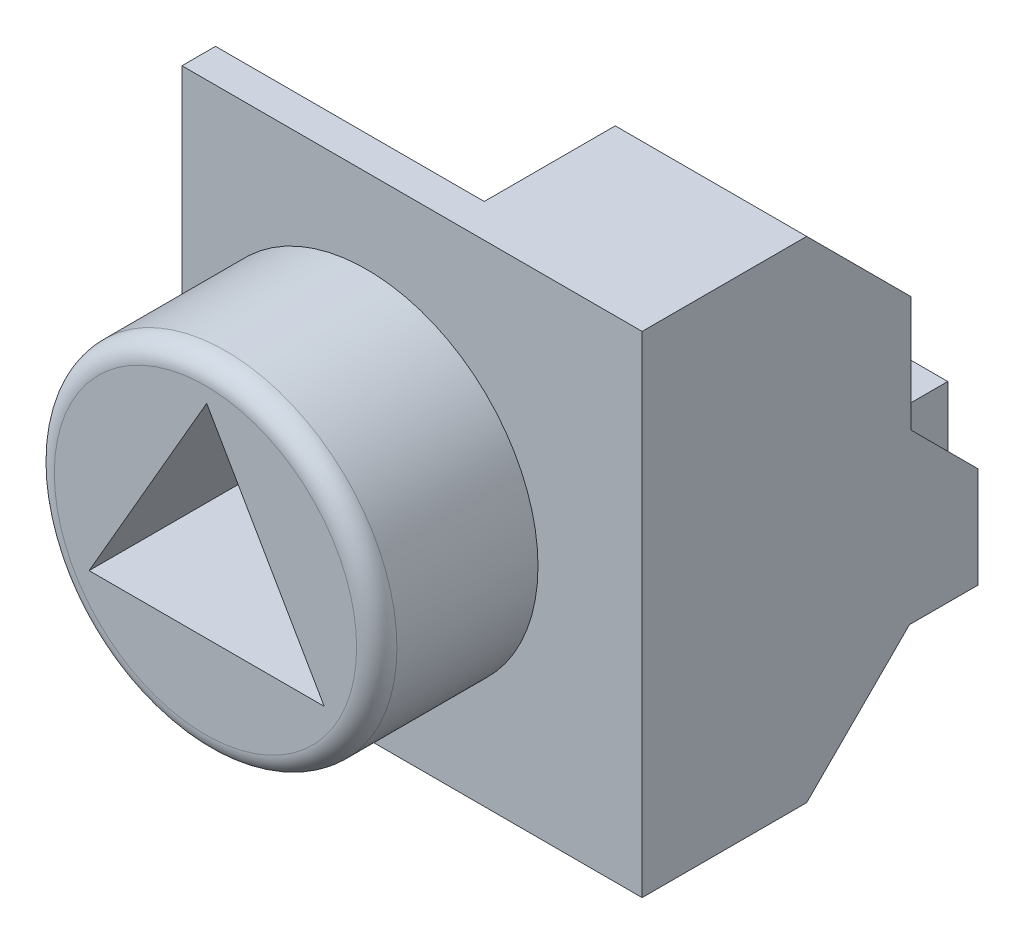
SolidWorks part; units mm, degrees
ref_plane "Спереди" through (0, 0, 0) normal (0, 0, 1) x (1, 0, 0)
ref_plane "Сверху" through (0, 0, 0) normal (0, 1, 0) x (1, 0, 0)
ref_plane "Справа" through (0, 0, 0) normal (1, 0, 0) x (0, 0, -1)
sketch "Эскиз1" plane through (0, 0, 0) normal (0, 0, 1) x (1, 0, 0)
  line L0 (-5, -15.52) -> (5, -15.52)
  line L1 (-5, 2.08) -> (5, 2.08)
  line L2 (0.9, -34.5) -> (0.9, 34.5)
  line L3 (5, 1.08) -> (-5, 1.08)
  line L4 (5, 17.48) -> (-5, 17.48)
  circle A0 centre (0, -6.52) radius 5.5
  circle A1 centre (0, 9.48) radius 5.5
  arc A2 (3.6151, 7.0385) -> (5.2151, 7.0385) centre (4.4151, 7.0385) ccw
  arc A3 (5.2151, 7.0385) -> (3.6151, 7.0385) centre (4.4151, 7.0385) ccw
  arc A4 (3.6151, -8.9615) -> (5.2151, -8.9615) centre (4.4151, -8.9615) ccw
  arc A5 (5.2151, -8.9615) -> (3.6151, -8.9615) centre (4.4151, -8.9615) ccw
sketch "Эскиз2" plane through (0, 0, 0) normal (0, 0, 1) x (1, 0, 0)
  circle A0 centre (0, 9.48) radius 5.1
  circle A1 centre (0, 9.48) radius 5.5 construction
  dimension "D1" = 0.4
extrude "Бобышка-Вытянуть1" add sketch "Эскиз2" along normal blind 4.8
sketch "Эскиз3" plane through (0, 0, 0) normal (0, 0, -1) x (-1, 0, 0)
  line L0 (-5, 17.48) -> (5, 17.48) construction
  line L1 (-5.5, 17.08) -> (5.5, 17.08)
  line L2 (-5.5, 17.08) -> (-5.5, 2.48)
  line L3 (-5.5, 2.48) -> (5.5, 2.48)
  line L4 (5.5, 17.08) -> (5.5, 2.48)
  line L5 (5, 2.08) -> (-5, 2.08) construction
  circle A0 centre (0, 9.48) radius 5.5 construction
  dimension "D1" = 0.4
  dimension "D2" = 0.4
extrude "Бобышка-Вытянуть2" add sketch "Эскиз3" along normal blind 1
sketch "Эскиз4" plane through (0, 0, -1) normal (0, 0, -1) x (-1, 0, 0)
  circle A0 centre (-4.4151, 7.0385) radius 1.5
  dimension "D1" = 3
extrude "Бобышка-Вытянуть3" add sketch "Эскиз4" along normal blind 10.8
sketch "Эскиз5" plane through (0, 0, -1) normal (0, 0, 1) x (1, 0, 0)
  line L1 (5.5, 8.0744) -> (5.5, 6.0026)
  line L2 (5.5, 8.0744) -> (5.5, 6.0026)
  arc A1 (5.5, 6.0026) -> (5.5, 8.0744) centre (4.4151, 7.0385) ccw
  arc A2 (5.5, 6.0026) -> (5.5, 8.0744) centre (4.4151, 7.0385) ccw
  dimension "D1" = 0
extrude "Вырез-Вытянуть1" cut sketch "Эскиз5" against normal blind 10.8
fillet "Скругление1" radius 0.6 1 edges at (5.1, 9.48, 4.8)
sketch "Эскиз6" plane through (0, 0, 4.8) normal (0, 0, 1) x (1, 0, 0)
  line L0 (0.0359, 13.5422) -> (-3.4641, 7.48)
  line L1 (-3.4641, 7.48) -> (3.5359, 7.48)
  line L2 (3.5359, 7.48) -> (0.0359, 13.5422)
  circle A0 centre (0, 9.48) radius 4.5 construction
  dimension "D1" = 7
  dimension "D2" = 7
  dimension "D3" = 7
  dimension "D4" = 2
  dimension "D5" = 2
extrude "Вырез-Вытянуть2" cut sketch "Эскиз6" against normal blind 4.8
sketch "Эскиз7" plane through (0, 0, 0) normal (0, 0, 1) x (1, 0, 0)
  circle A0 centre (0, 9.48) radius 1
  dimension "D1" = 2
extrude "Вырез-Вытянуть3" cut sketch "Эскиз7" against normal blind 1
sketch "Эскиз8" plane through (0, 0, -1) normal (0, 0, -1) x (-1, 0, 0)
  line L0 (-5.5, 2.48) -> (5.5, 2.48) construction
  line L1 (-5.5, 17.08) -> (-2.5, 17.08)
  line L2 (-5.5, 17.08) -> (-5.5, 2.48)
  line L3 (-5.5, 2.48) -> (-2.5, 2.48)
  line L4 (-2.5, 17.08) -> (-2.5, 2.48)
  dimension "D1" = 3
extrude "Бобышка-Вытянуть4" add sketch "Эскиз8" along normal blind 7
chamfer "Фаска1" distance 3.1 angle 45 2 edges at (4, 2.48, -8) (4, 17.08, -8)
sketch "Эскиз9" plane through (0, 0, -11.8) normal (0, 0, -1) x (-1, 0, 0)
  line L0 (-5.5, 6.0026) -> (-5.5, 5.58) construction
  line L1 (-5.5, 5.5385) -> (-2.9151, 5.5385)
  line L2 (-5.5, 5.5385) -> (-5.5, 8.5385)
  line L3 (-5.5, 8.5385) -> (-2.9151, 8.5385)
  line L4 (-2.9151, 5.5385) -> (-2.9151, 8.5385)
extrude "Бобышка-Вытянуть5" add sketch "Эскиз9" against normal blind 10
chamfer "Фаска3" distance 2 angle 45 1 edges at (4.2076, 8.5385, -8)
chamfer "Фаска4" distance 2 angle 45 1 edges at (2.9151, 8.0592, -8)
sketch "Эскиз10" plane through (5.5, 0, 0) normal (1, 0, 0) x (0, 0, -1)
  line L0 (10, 8.5385) -> (10, 5.5385)
  line L10 (11.8, 8.5385) -> (10, 8.5385)
  line L11 (10, 8.5385) -> (8, 10.5385)
  line L12 (8, 10.5385) -> (8, 13.98)
  line L13 (8, 13.98) -> (4.9, 17.08)
  line L14 (4.9, 17.08) -> (0, 17.08)
  line L15 (0, 17.08) -> (0, 2.48)
  line L16 (0, 2.48) -> (4.9, 2.48)
  line L17 (4.9, 2.48) -> (7.9585, 5.5385)
  line L18 (7.9585, 5.5385) -> (11.8, 5.5385)
  line L19 (11.8, 5.5385) -> (11.8, 8.5385)
  line L20 (11.8, 8.5385) -> (10, 8.5385)
  line L21 (10, 8.5385) -> (8, 10.5385)
  line L22 (8, 10.5385) -> (8, 13.98)
  line L23 (8, 13.98) -> (4.9, 17.08)
  line L24 (4.9, 17.08) -> (0, 17.08)
  line L25 (0, 17.08) -> (0, 2.48)
  line L26 (0, 2.48) -> (4.9, 2.48)
  line L27 (4.9, 2.48) -> (7.9585, 5.5385)
  line L28 (7.9585, 5.5385) -> (11.8, 5.5385)
  line L29 (11.8, 5.5385) -> (11.8, 8.5385)
  line M12 (10, 8.5385) -> (8, 10.5385)
  line M13 (8, 10.5385) -> (8, 13.98)
  line M14 (8, 13.98) -> (4.9, 17.08)
  line M15 (4.9, 17.08) -> (0, 17.08)
  line M16 (0, 17.08) -> (0, 2.48)
  line M17 (0, 2.48) -> (4.9, 2.48)
  line M18 (4.9, 2.48) -> (7.9585, 5.5385)
  line M19 (7.9585, 5.5385) -> (11.8, 5.5385)
  dimension "D1" = 0
extrude "Бобышка-Вытянуть6" add sketch "Эскиз10" along normal blind 2.7 contours L0 M12 M13 M14 M15 M16 M17 M18 M19 region at (5.5, 9.6272, -4.094)
